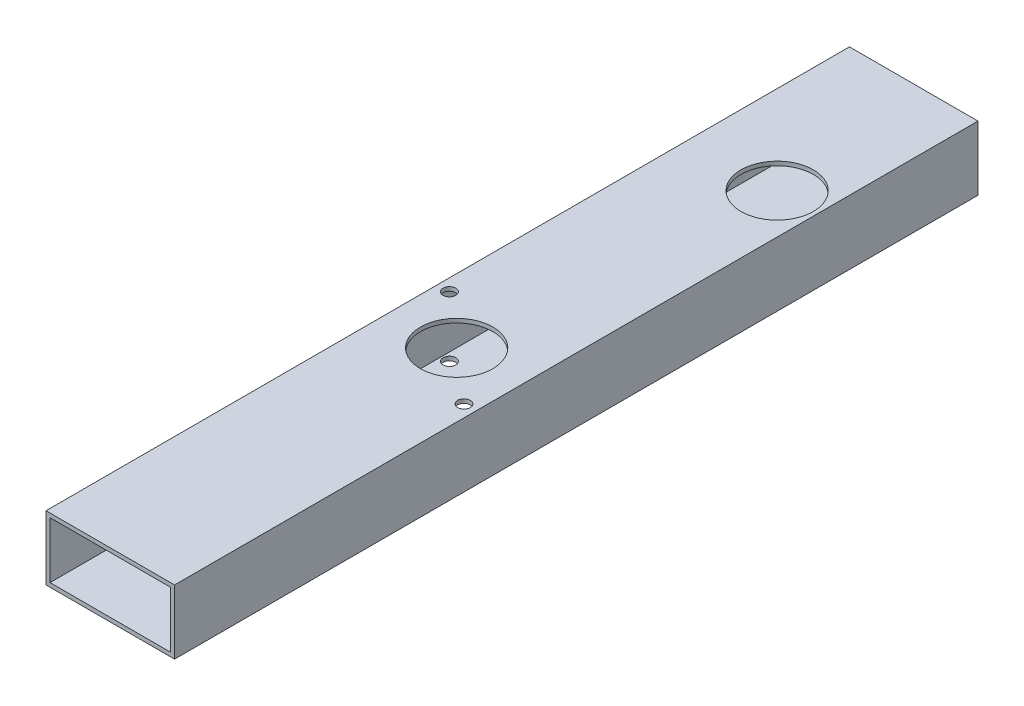
SolidWorks part; units mm, degrees
ref_plane "Front Plane" through (0, 0, 0) normal (0, 0, 1) x (1, 0, 0)
ref_plane "Top Plane" through (0, 0, 0) normal (0, 1, 0) x (1, 0, 0)
ref_plane "Right Plane" through (0, 0, 0) normal (1, 0, 0) x (0, 0, -1)
sketch "Sketch1" plane through (0, 0, 0) normal (0, 0, 1) x (1, 0, 0)
  line L0 (-23.8125, 11.1125) -> (23.8125, 11.1125)
  line L2 (-25.4, 12.7) -> (25.4, 12.7)
  line L3 (-25.4, 12.7) -> (-25.4, -12.7)
  line L4 (-25.4, -12.7) -> (25.4, -12.7)
  line L5 (25.4, 12.7) -> (25.4, -12.7)
  line L10 (23.8125, 11.1125) -> (23.8125, -11.1125)
  line L11 (-23.8125, -11.1125) -> (23.8125, -11.1125)
  line L12 (-23.8125, 11.1125) -> (-23.8125, -11.1125)
  point P12 (0, 12.7)
  point P14 (25.4, 0)
  dimension "Wall Thickness" = 1.5875
  dimension "Outside Width" = 50.8
  dimension "Outside Height" = 25.4
  dimension "Inside Height" = 22.225
  dimension "Inside Width" = 47.625
sketch "Sketch2" plane through (0, 0, 0) normal (1, 0, 0) x (0, 0, -1)
  line L0 (158.75, 0) -> (-158.75, 0)
  point P4 (0, 0)
  point P7 (-158.75, 0)
  point P10 (158.75, 0)
  dimension "Length" = 317.5
sketch "Sketch3" plane through (0, 0, 0) normal (0, 0, 1) x (1, 0, 0)
  line L21 (25.4, 12.7) -> (-25.4, 12.7)
  line L22 (25.4, -12.7) -> (25.4, 12.7)
  line L23 (-25.4, -12.7) -> (25.4, -12.7)
  line L24 (-25.4, 12.7) -> (-25.4, -12.7)
  line L25 (25.4, 12.7) -> (-25.4, 12.7)
  line L26 (25.4, -12.7) -> (25.4, 12.7)
  line L27 (-25.4, -12.7) -> (25.4, -12.7)
  line L28 (-25.4, 12.7) -> (-25.4, -12.7)
  line L29 (23.8125, 11.1125) -> (-23.8125, 11.1125)
  line L30 (23.8125, -11.1125) -> (23.8125, 11.1125)
  line L31 (-23.8125, -11.1125) -> (23.8125, -11.1125)
  line L32 (-23.8125, 11.1125) -> (-23.8125, -11.1125)
  line L33 (23.8125, 11.1125) -> (-23.8125, 11.1125)
  line L34 (23.8125, -11.1125) -> (23.8125, 11.1125)
  line L35 (-23.8125, -11.1125) -> (23.8125, -11.1125)
  line L36 (-23.8125, 11.1125) -> (-23.8125, -11.1125)
  dimension "D1" = 0
  dimension "D2" = 0
extrude "Boss-Extrude1" add sketch "Sketch3" along normal up to vertex (158.75 mm away) and the other way up to vertex (158.75 mm away) up to point (0, 0, 158.75) other way up to point (0, 0, -158.75)
sketch "Drawing Reference" plane through (0, 0, 0) normal (1, 0, 0) x (0, 0, -1)
  line L0 (-158.75, 0) -> (158.75, 0) construction
  line L1 (0, -12.7) -> (0, 12.7) construction
  line L2 (-158.75, -12.7) -> (158.75, -12.7) construction
  line L5 (-158.75, 12.7) -> (158.75, 12.7) construction
  point P7 (-122.174, 0)
  point P8 (122.174, 0)
  dimension "D1" = 36.576
sketch "Sketch4" plane through (0, 12.7, 0) normal (0, 1, 0) x (1, 0, 0)
  line L0 (0, 158.75) -> (0, 95.25) construction
  line L1 (25.4, 158.75) -> (-25.4, 158.75) construction
  line L2 (0, 95.25) -> (9.525, 95.25) construction
  line L3 (0, 158.75) -> (0, -26.67) construction
  circle A1 centre (9.525, 95.25) radius 14.2875
  circle A3 centre (9.525, 95.25) radius 117.5004 construction
  circle A4 centre (0, -21.8637) radius 14.2875
  dimension "D1" = 63.5
  dimension "D3" = 235.0008
  dimension "D2" = 9.525
extrude "Cut-Extrude1" cut sketch "Sketch4" against normal blind 39.37
sketch "Sketch6" plane through (0, 12.7, 0) normal (0, 1, 0) x (1, 0, 0)
  line L0 (-20.6308, -4.1018) -> (20.6308, -39.6256) construction
  circle A0 centre (0, -21.8637) radius 27.2234 construction
  point P8 (0, -21.8637)
hole_wizard "#10 Clearance Hole1" positions "Sketch7" profile "Sketch8" hole size "#10" standard "ANSI Inch" end condition through all
sketch "Sketch7" plane through (0, 12.7, 0) normal (0, 1, 0) x (1, 0, 0)
  point P0 (-20.6308, -4.1018)
  point P3 (20.6308, -39.6256)
  point P7 (0, 0)
  point P8 (-17.9605, -37.3266)
  point P9 (17.9605, -37.3266)
  point P11 (-17.9605, -1.4056)
sketch "Sketch8" plane through (-20.6308, 12.7, 4.1018) normal (1, 0, 0) x (0, 0, 1)
  line L0 (0, 0) -> (0, 25.4)
  line L1 (0, 25.4) -> (2.4892, 25.4)
  line L2 (2.4892, 25.4) -> (2.4892, 0)
  line L5 (2.4892, 0) -> (0, 0)
  line L11 (0, -6.35) -> (0, 107.95) construction
  dimension "Thru Hole Dia." = 4.9784
  dimension "Thru Hole Depth" = 25.4
equation "\"D1@Drawing Reference\"=\"Outside Width@Sketch1\" * 0.72"
